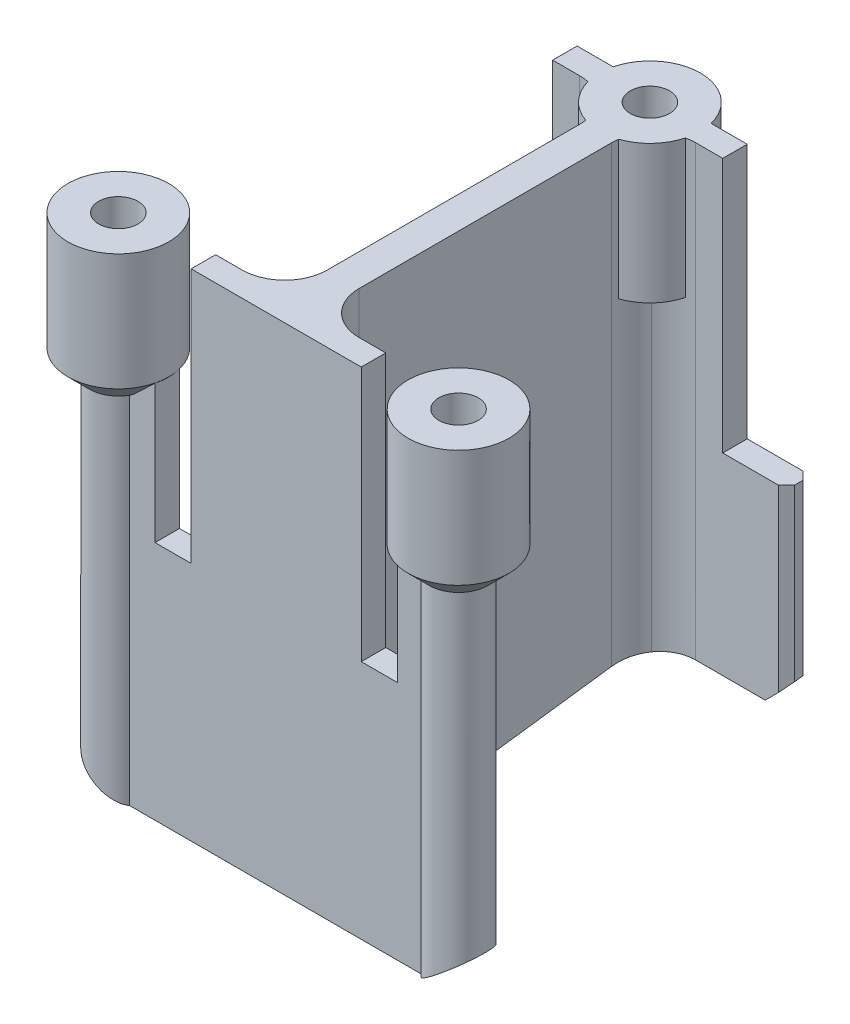
SolidWorks part; units mm, degrees
ref_plane "Front Plane" through (0, 0, 0) normal (0, 0, 1) x (1, 0, 0)
ref_plane "Top Plane" through (0, 0, 0) normal (0, 1, 0) x (1, 0, 0)
ref_plane "Right Plane" through (0, 0, 0) normal (1, 0, 0) x (0, 0, -1)
sketch "Sketch1" plane through (0, 0, 0) normal (0, 1, 0) x (1, 0, 0)
  line L0 (0, -1.15) -> (0, -24.4762) construction
  line L1 (-1.5, 1.15) -> (-1.5, -1.15) construction
  line L2 (-13.7802, 1.15) -> (-1.5, 1.15)
  line L3 (-13.7802, 1.15) -> (-13.7802, -1.15) construction
  line L4 (-13.7802, -1.15) -> (13.7802, -1.15)
  line L5 (13.7802, 1.15) -> (13.7802, -1.15) construction
  line L6 (-1.5, 30.8377) -> (1.5, 30.8377) construction
  line L7 (-1.5, 30.8377) -> (-1.5, 1.15)
  line L8 (-1.5, -1.15) -> (1.5, -1.15)
  line L9 (1.5, 30.8377) -> (1.5, 1.15)
  line L10 (0, 0) -> (0, -1.15) construction
  line L11 (1.5, 1.15) -> (1.5, -1.15) construction
  line L12 (-1.5, 1.15) -> (1.5, 1.15) construction
  line L13 (1.5, 1.15) -> (13.7802, 1.15)
  line L14 (-3.3057, 35.15) -> (3.3057, 35.15) construction
  line L15 (-14, 32.85) -> (-3.3057, 32.85)
  line L16 (-14, 32.85) -> (-14, 35.15)
  line L17 (-14, 35.15) -> (-3.3057, 35.15)
  line L18 (14, 32.85) -> (14, 35.15)
  line L19 (-14, 32.85) -> (-3.4883, 33.7135) construction
  line L20 (-14, 35.15) -> (-3.4883, 34.2865) construction
  line L21 (3.3057, 35.15) -> (14, 35.15)
  line L22 (-3.4883, 34.2865) -> (0, 34) construction
  line L23 (0, 34) -> (3.4883, 33.7135) construction
  line L24 (-3.4883, 33.7135) -> (0, 34) construction
  line L25 (3.4883, 34.2865) -> (14, 35.15) construction
  line L26 (-3.3057, 32.85) -> (3.3057, 32.85) construction
  line L27 (3.3057, 32.85) -> (14, 32.85)
  line L28 (0, 34) -> (3.4883, 34.2865) construction
  line L29 (3.4883, 33.7135) -> (14, 32.85) construction
  arc A0 (-13.7802, 1.15) -> (-13.7802, -1.15) centre (-16, 0) ccw
  arc A1 (13.7802, -1.15) -> (13.7802, 1.15) centre (16, 0) ccw
  arc A2 (1.5, 30.8377) -> (3.3057, 32.85) centre (0, 34) ccw
  arc A3 (13.7802, 1.15) -> (13.7802, -1.15) centre (16, 0) ccw construction
  arc A4 (-13.7802, -1.15) -> (-13.7802, 1.15) centre (-16, 0) ccw construction
  arc A5 (-1.5, 30.8377) -> (1.5, 30.8377) centre (0, 34) ccw construction
  arc A6 (3.4883, 33.7135) -> (3.4883, 34.2865) centre (0, 34) ccw construction
  arc A7 (3.3057, 35.15) -> (-3.3057, 35.15) centre (0, 34) ccw
  arc A8 (-3.4883, 34.2865) -> (-3.4883, 33.7135) centre (0, 34) ccw construction
  arc A9 (-3.3057, 32.85) -> (-1.5, 30.8377) centre (0, 34) ccw
  arc A10 (-3.3057, 35.15) -> (-3.4883, 34.2865) centre (0, 34) ccw construction
  arc A11 (3.4883, 34.2865) -> (3.3057, 35.15) centre (0, 34) ccw construction
  arc A12 (3.3057, 32.85) -> (3.4883, 33.7135) centre (0, 34) ccw construction
  arc A13 (-3.4883, 33.7135) -> (-3.3057, 32.85) centre (0, 34) ccw construction
  dimension "D1" = 5
  dimension "D8" = 3.5
  dimension "D2" = 16
  dimension "D3" = 34
  dimension "D4" = 3
  dimension "D5" = 2.3
  dimension "D6" = 2.3
  dimension "D7" = 28
extrude "Boss-Extrude1" add sketch "Sketch1" against normal blind 46.8 contours L9 A2 L7 L2 A0 L4 A1 L13 region at (0, 0, -15.7411)
sketch "Sketch3" plane through (0, 0, 0) normal (1, 0, 0) x (0, 0, -1)
  line L0 (-2.5, -46.8) -> (48.8365, -40.0323)
  line L1 (48.8365, -40.0323) -> (48.8365, -52.4526)
  line L2 (48.8365, -52.4526) -> (-2.5, -52.4526)
  line L3 (-2.5, -52.4526) -> (-2.5, -46.8)
  line L4 (-2.5, -46.8) -> (-2.5, -23.9782) construction
  line L5 (-2.5, 0) -> (-2.5, -46.8) construction
  dimension "D1" = 82.49
extrude "Cut-Extrude1" cut sketch "Sketch3" against normal through all both and the other way through all
sketch "Sketch4" plane through (0, 0, 0) normal (0, 1, 0) x (1, 0, 0)
  line L0 (0, -23.925) -> (0, 23.925) construction
  line L1 (-22.825, 0) -> (22.825, 0) construction
  circle A0 centre (0, 34) radius 5
  circle A1 centre (16, 0) radius 5
  circle A2 centre (-16, 0) radius 5
  arc A3 (-13.7802, 1.15) -> (-13.7802, -1.15) centre (-16, 0) ccw construction
  arc A4 (1.5, 30.8377) -> (3.3057, 32.85) centre (0, 34) ccw construction
  dimension "D1" = 10
extrude "Boss-Extrude2" [suppressed] add sketch "Sketch4" along normal blind 16.8
fillet "Fillet1" radius 4 6 edges at (1.5, -21.2025, -30.8377) (3.3057, -21.0699, -32.85) (-3.3057, -21.0699, -32.85) (-1.5, -21.2025, -30.8377) (-1.5, -23.1594, -1.15) (1.5, -23.1594, -1.15)
fillet "Fillet2" [suppressed] radius 4
fillet "Fillet3" [suppressed] radius 4
fillet "Fillet4" [suppressed] radius 4
chamfer "Chamfer1" distance 0.75 angle 45 4 edges at (-14, -21.0699, -32.85) (-14, -20.9183, -35.15) (14, -20.9183, -35.15) (14, -21.0699, -32.85)
sketch "Sketch5" plane through (0, 0, 0) normal (0, 1, 0) x (1, 0, 0)
  line L0 (-13.25, 35.15) -> (-3.3057, 35.15) construction
  line L1 (-11.4, 35.15) -> (-8, 35.15)
  line L2 (-11.4, 29.5378) -> (-11.4, -1.15)
  line L3 (-11.4, -1.15) -> (-8, -1.15)
  line L4 (-8, 35.15) -> (-8, -1.15)
  line L5 (-13.7802, -1.15) -> (13.7802, -1.15) construction
  line L6 (0, -23.925) -> (0, 23.925) construction
  line L7 (-11.4, 35.15) -> (-11.4, 29.5378) construction
  line L8 (-18.2995, 37.6377) -> (-11.4, 37.6377)
  line L9 (-18.2995, 37.6377) -> (-18.2995, 29.5378)
  line L10 (-18.2995, 29.5378) -> (-11.4, 29.5378)
  line L11 (-11.4, 37.6377) -> (-11.4, 35.15)
  line L12 (-11.4, 35.15) -> (-11.4, 29.5378) construction
  line L13 (11.4, 37.6377) -> (11.4, 35.15)
  line L14 (18.2995, 37.6377) -> (11.4, 37.6377)
  line L15 (18.2995, 37.6377) -> (18.2995, 29.5378)
  line L16 (18.2995, 29.5378) -> (11.4, 29.5378)
  line L17 (11.4, 29.5378) -> (11.4, -1.15)
  line L18 (11.4, -1.15) -> (8, -1.15)
  line L19 (8, 35.15) -> (8, -1.15)
  line L20 (11.4, 35.15) -> (8, 35.15)
  dimension "D1" = 3.4
  dimension "D2" = 8
extrude "Cut-Extrude2" cut sketch "Sketch5" against normal blind 24
sketch "Sketch6" plane through (0, 0, 0) normal (0, 1, 0) x (1, 0, 0)
  line L0 (0, -23.925) -> (0, 23.925) construction
  line L1 (-22.825, 0) -> (22.825, 0) construction
  circle A0 centre (0, 34) radius 4.75
  circle A1 centre (16, 0) radius 4.75
  circle A2 centre (-16, 0) radius 4.75
  arc A3 (-13.7802, 1.15) -> (-13.7802, -1.15) centre (-16, 0) ccw construction
  arc A4 (3.3057, 35.15) -> (-3.3057, 35.15) centre (0, 34) ccw construction
  arc A5 (13.7802, -1.15) -> (13.7802, 1.15) centre (16, 0) ccw construction
  dimension "D1" = 9.5
extrude "Boss-Extrude3" add sketch "Sketch6" against normal blind 13
hole_wizard "M3 Clearance Hole1" positions "Sketch8" profile "Sketch10" hole size "M3" standard "ANSI Metric"
sketch "Sketch8" plane through (0, 0, 0) normal (0, 1, 0) x (1, 0, 0)
  line L0 (0, -23.925) -> (0, 23.925) construction
  circle A0 centre (0, 34) radius 4.75 construction
  arc A2 (4.6087, 35.15) -> (-4.6087, 35.15) centre (0, 34) ccw construction
  point P0 (-16, 0)
  point P3 (16, 0)
  point P6 (0, 34)
sketch "Sketch10" plane through (-16, 0, 0) normal (1, 0, 0) x (0, 0, 1)
  line L0 (0, 0) -> (0, 13.6116)
  line L1 (0, 13.6116) -> (1.85, 12.5)
  line L2 (1.85, 12.5) -> (1.85, 0)
  line L5 (1.85, 0) -> (0, 0)
  line L10 (0, 13.6116) -> (-1.85, 12.5) construction
  line L11 (0, -6.35) -> (0, 107.95) construction
  dimension "Hole Dia." = 3.7
  dimension "Hole Depth" = 12.5
  dimension "Drill Angle" = 118
ref_plane "Plane1" through (0, -10, 0) normal (0, 1, 0) x (1, 0, 0)
sketch "Sketch11" plane through (0, -10, 0) normal (0, 1, 0) x (1, 0, 0)
  line L0 (0, -23.925) -> (0, 23.925) construction
  line L31 (-16, 3.7528) -> (-19.25, 1.8764) construction
  line L32 (-19.25, 1.8764) -> (-19.25, -1.8764)
  line L33 (-19.25, -1.8764) -> (-16, -3.7528)
  line L34 (-16, -3.7528) -> (-12.75, -1.8764)
  line L35 (-12.75, -1.8764) -> (-12.75, 1.8764)
  line L36 (-12.75, 1.8764) -> (-16, 3.7528) construction
  line L37 (16, 3.7528) -> (12.75, 1.8764) construction
  line L38 (12.75, 1.8764) -> (12.75, -1.8764)
  line L40 (12.75, -1.8764) -> (16, -3.7528)
  line L41 (16, -3.7528) -> (19.25, -1.8764)
  line L42 (19.25, -1.8764) -> (19.25, 1.8764)
  line L43 (19.25, 1.8764) -> (16, 3.7528) construction
  line L44 (0, 37.7528) -> (-3.25, 35.8764) construction
  line L45 (-3.25, 35.8764) -> (-3.25, 32.1236)
  line L46 (-3.25, 32.1236) -> (0, 30.2472)
  line L47 (0, 30.2472) -> (3.25, 32.1236)
  line L48 (3.25, 32.1236) -> (3.25, 35.8764)
  line L49 (3.25, 35.8764) -> (0, 37.7528) construction
  line L50 (-3.25, 35.8764) -> (-3.25, 39.9061)
  line L51 (-3.25, 39.9061) -> (3.25, 39.9061)
  line L52 (3.25, 39.9061) -> (3.25, 35.8764)
  line L53 (-19.25, 1.8764) -> (-19.25, 7.9963)
  line L54 (-19.25, 7.9963) -> (-12.75, 7.9963)
  line L55 (-12.75, 7.9963) -> (-12.75, 1.8764)
  line L56 (12.75, 1.8764) -> (12.75, 7.9963)
  line L57 (12.75, 7.9963) -> (19.25, 7.9963)
  line L58 (19.25, 7.9963) -> (19.25, 1.8764)
  circle A1 centre (-16, 0) radius 3.25 construction
  circle A5 centre (16, 0) radius 3.25 construction
  circle A6 centre (0, 34) radius 3.25 construction
  dimension "D1" = 6.5
extrude "Cut-Extrude3" cut sketch "Sketch11" along normal blind 3.5 contours L40 L41 | L48 L54 L46 L47 | L35 L33 L34 region at (-16, -10, -2.5773) region at (16, -10, -2.5773) region at (0, -10, -35.5289)
sketch "Sketch12" plane through (0, 0, 1.15) normal (0, 0, 1) x (1, 0, 0)
  line L0 (-14.4, -46.622) -> (-18.5, -21.622)
  line L1 (13.7802, -46.622) -> (-13.7802, -46.622) construction
  line L2 (-18.5, -13) -> (-18.5, -46.4704) construction
  line L3 (-18.5, -21.622) -> (-31.9745, -21.622)
  line L4 (-31.9745, -21.622) -> (-31.9745, -49.8286)
  line L5 (-31.9745, -49.8286) -> (-14.4, -49.8286)
  line L6 (-14.4, -49.8286) -> (-14.4, -46.622)
  line L7 (-11.4, -24) -> (-11.4, -13) construction
  dimension "D1" = 3
  dimension "D2" = 25
sketch "Sketch13" plane through (0, 0, 1.15) normal (0, 0, 1) x (1, 0, 0)
  line L0 (-13.7802, -46.622) -> (-20.3603, -41.622)
  line L1 (-20.3603, -41.622) -> (-20.3603, -47.9492)
  line L2 (-20.3603, -47.9492) -> (-13.7802, -47.9492)
  line L3 (-13.7802, -47.9492) -> (-13.7802, -46.622)
  line L4 (13.7802, -46.622) -> (-13.7802, -46.622) construction
  dimension "D1" = 5
extrude "Cut-Extrude5" cut sketch "Sketch13" against normal through all both and the other way through all
chamfer "Chamfer2" distance 2 angle 45 2 edges at (14, -41.9882, -34) (-14, -41.9882, -34)
mirror "Mirror1" about plane through (0, 0, 0) normal (1, 0, 0) of "Cut-Extrude5"
extrude "Cut-Extrude4" [suppressed] cut sketch "Sketch12" against normal through all both and the other way through all
chamfer "Chamfer3" distance 2 angle 45 3 edges at (16, -13, 4.75) (-16, -13, 4.75) (0, -13, -38.75)
